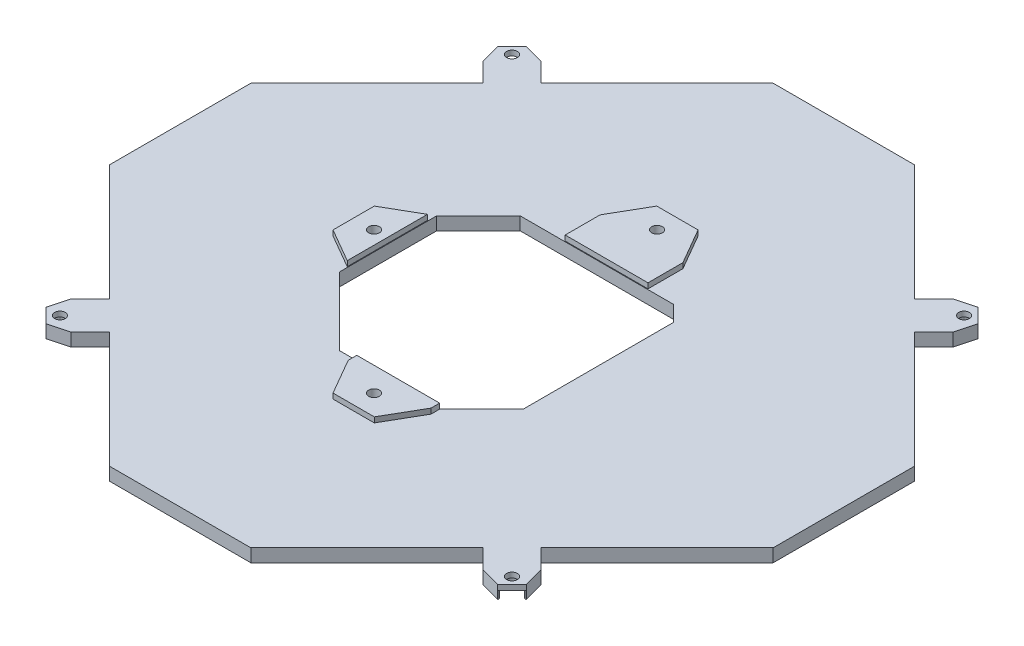
SolidWorks part; units mm, degrees
ref_plane "Front Plane" through (0, 0, 0) normal (0, 0, 1) x (1, 0, 0)
ref_plane "Top Plane" through (0, 0, 0) normal (0, 1, 0) x (1, 0, 0)
ref_plane "Right Plane" through (0, 0, 0) normal (1, 0, 0) x (0, 0, -1)
sketch "Sketch1" plane through (0, -273.8462, 0) normal (0, -1, 0) x (-1, 0, 0)
  line L0 (82.3028, 71.3418) -> (89.3773, 78.4163)
  line L1 (89.3773, 78.4163) -> (91.3931, 85.9396)
  line L2 (91.3931, 85.9396) -> (85.9404, 91.3923)
  line L3 (85.9404, 91.3923) -> (78.4171, 89.3765)
  line L4 (78.4171, 89.3765) -> (71.3427, 82.302)
  line L5 (82.3028, 71.3418) -> (82.02, 71.059)
  line L6 (71.3427, 82.302) -> (71.0598, 82.0192)
  line L7 (71.3418, -82.3028) -> (78.4163, -89.3773)
  line L8 (78.4163, -89.3773) -> (85.9396, -91.3931)
  line L9 (85.9396, -91.3931) -> (91.3923, -85.9404)
  line L10 (91.3923, -85.9404) -> (89.3765, -78.4171)
  line L11 (89.3765, -78.4171) -> (82.302, -71.3427)
  line L12 (71.3418, -82.3028) -> (71.059, -82.02)
  line L13 (82.302, -71.3427) -> (82.0192, -71.0598)
  line L14 (126.6447, 27) -> (126.6447, -27) construction
  line L15 (27, -126.6455) -> (-27, -126.6455) construction
  line L16 (-126.6447, -27) -> (-126.6447, 27) construction
  line L17 (-27, 126.6447) -> (27, 126.6447) construction
  line L18 (126.6447, 27) -> (126.6447, -27) construction
  line L19 (27, -126.6455) -> (-27, -126.6455) construction
  line L20 (-126.6447, -27) -> (-126.6447, 27) construction
  line L21 (-27, 126.6447) -> (27, 126.6447) construction
  line L22 (-126.6447, 27) -> (-27, 126.6447) construction
  line L23 (27, 126.6447) -> (126.6447, 27) construction
  line L24 (126.6447, -27) -> (27, -126.6455) construction
  line L25 (-27, -126.6455) -> (-126.6447, -27) construction
  line L26 (-26.8343, -126.2455) -> (-71.0601, -82.0194)
  line L27 (-126.2447, -26.8343) -> (-126.2447, 26.8343)
  line L28 (-28.1456, -5.25) -> (-32.9992, -5.25)
  line L29 (-32.9992, -5.25) -> (-32.9992, -28.4962)
  line L30 (-32.9992, -28.4962) -> (-17.0954, -44.4)
  line L31 (-17.0954, -44.4) -> (21.2718, -44.4)
  line L32 (21.2718, -44.4) -> (47.1756, -18.4962)
  line L33 (47.1756, -18.4962) -> (47.1756, 18.4962)
  line L34 (47.1756, 18.4962) -> (31.2718, 34.4)
  line L35 (31.2718, 34.4) -> (-27.0954, 34.4)
  line L36 (-27.0954, 34.4) -> (-32.9992, 28.4962)
  line L37 (-32.9992, 28.4962) -> (-32.9992, 5.25)
  line L38 (-32.9992, 5.25) -> (-28.1456, 5.25)
  line L39 (-28.1456, 5.25) -> (-21.4992, 11.8964)
  line L40 (-21.4992, 11.8964) -> (-21.4992, -11.8964)
  line L41 (-21.4992, -11.8964) -> (-28.1456, -5.25)
  line L42 (-28.1456, -5.25) -> (-32.9992, -5.25) construction
  line L43 (-32.9992, -5.25) -> (-32.9992, -28.4962)
  line L44 (-32.9992, -28.4962) -> (-17.0954, -44.4)
  line L45 (-17.0954, -44.4) -> (21.2718, -44.4)
  line L46 (21.2718, -44.4) -> (47.1756, -18.4962)
  line L47 (47.1756, -18.4962) -> (47.1756, 18.4962)
  line L48 (47.1756, 18.4962) -> (31.2718, 34.4)
  line L49 (31.2718, 34.4) -> (-27.0954, 34.4)
  line L50 (-27.0954, 34.4) -> (-32.9992, 28.4962)
  line L51 (-32.9992, 28.4962) -> (-32.9992, 5.25)
  line L52 (-32.9992, 5.25) -> (-28.1456, 5.25) construction
  line L53 (-28.1456, 5.25) -> (-21.4992, 11.8964) construction
  line L54 (-21.4992, 11.8964) -> (-21.4992, -11.8964) construction
  line L55 (-21.4992, -11.8964) -> (-28.1456, -5.25) construction
  line L56 (-126.2447, 26.8343) -> (-82.0192, 71.0598)
  line L57 (-26.8343, 126.2447) -> (26.8343, 126.2447)
  line L58 (26.8343, 126.2447) -> (71.0598, 82.0192)
  line L59 (126.2447, 26.8343) -> (126.2447, -26.8343)
  line L60 (126.2447, -26.8343) -> (82.0193, -71.06)
  line L61 (26.8343, -126.2455) -> (-26.8343, -126.2455)
  line L62 (-82.3028, -71.3418) -> (-89.3773, -78.4163)
  line L63 (-89.3773, -78.4163) -> (-91.3931, -85.9396)
  line L64 (-91.3931, -85.9396) -> (-85.9404, -91.3923)
  line L65 (-85.9404, -91.3923) -> (-78.4171, -89.3765)
  line L66 (-78.4171, -89.3765) -> (-71.3427, -82.302)
  line L67 (-71.3418, 82.3028) -> (-71.059, 82.02)
  line L68 (-82.302, 71.3427) -> (-82.0192, 71.0598)
  line L69 (-82.3028, -71.3418) -> (-82.02, -71.059)
  line L70 (-71.3427, -82.302) -> (-71.0598, -82.0192)
  line L71 (-82.0192, 71.0598) -> (-71.059, 82.02) construction
  line L72 (-71.3418, 82.3028) -> (-78.4163, 89.3773)
  line L73 (-78.4163, 89.3773) -> (-85.9396, 91.3931)
  line L74 (-85.9396, 91.3931) -> (-91.3923, 85.9404)
  line L75 (-89.3765, 78.4171) -> (-82.302, 71.3427)
  line L76 (-91.3923, 85.9404) -> (-89.3765, 78.4171)
  line L77 (-71.3418, 82.3028) -> (-78.4163, 89.3773)
  line L78 (-78.4163, 89.3773) -> (-85.9396, 91.3931)
  line L79 (-85.9396, 91.3931) -> (-91.3923, 85.9404)
  line L80 (-89.3765, 78.4171) -> (-82.302, 71.3427)
  line L81 (-91.3923, 85.9404) -> (-89.3765, 78.4171)
  line L82 (-71.059, 82.02) -> (-26.8343, 126.2447)
  line L83 (-126.2447, 26.8343) -> (-26.8343, 126.2447) construction
  line L84 (71.0598, 82.0192) -> (82.02, 71.059) construction
  line L85 (82.02, 71.059) -> (126.2447, 26.8343)
  line L86 (26.8343, 126.2447) -> (126.2447, 26.8343) construction
  line L87 (82.0193, -71.06) -> (71.0592, -82.0202) construction
  line L88 (71.0592, -82.0202) -> (26.8343, -126.2455)
  line L89 (126.2447, -26.8343) -> (26.8343, -126.2455) construction
  line L90 (-71.0601, -82.0194) -> (-82.0202, -71.0592) construction
  line L91 (-82.0202, -71.0592) -> (-126.2447, -26.8343)
  line L92 (-26.8343, -126.2455) -> (-126.2447, -26.8343) construction
  line L93 (-32.9992, 5.25) -> (-32.9992, -5.25)
  point P65 (0, 0)
  dimension "D1" = 0.25
  dimension "D2" = 0.4
  dimension "D3" = 0.25
  dimension "D4" = 4
extrude "Boss-Extrude1" add sketch "Sketch1" against normal offset from surface (4.95 mm away) 0.05 contours L91 L69 L62 L63 L64 L65 L66 L70 L26 L61 L88 L12 L7 L8 L9 L10 L11 L13 L60 L59 L85 L5 L0 L1 L2 L3 L4 L6 L58 L57 L82 L67 L77 L78 L79 L81 L80 L68 L56 L27 L93 L51 region at (-79.6365, -273.8462, -73.7253)
sketch "Sketch2" plane through (0, -268.8962, 0) normal (0, 1, 0) x (1, 0, 0)
  circle A0 centre (-86.0151, 86.0143) radius 2.05
  circle A1 centre (86.0143, 86.0151) radius 2.05
  circle A2 centre (86.0151, -86.0151) radius 2.05
  circle A3 centre (-86.015, -86.015) radius 2.05
  circle A5 centre (1.3492, 53.8564) radius 2.05
  circle A6 centre (-52.5072, 0) radius 2.05
  circle A7 centre (1.3492, -53.8564) radius 2.05
  dimension "D1" = 4.1
extrude "Cut-Extrude1" cut sketch "Sketch2" against normal through all
sketch "Sketch4" plane through (0, -268.8962, 0) normal (0, 1, 0) x (1, 0, 0)
  line L0 (17.3492, 48) -> (17.3492, 34.4) construction
  line L1 (27.0954, 34.4) -> (-31.2718, 34.4) construction
  line L2 (17.3492, 48) -> (17.3492, 34.15) construction
  line L3 (-14.6508, 48) -> (-14.6508, 34.4) construction
  line L4 (-14.6508, 34.15) -> (-14.6508, 48) construction
  line L5 (-14.6508, 34.4) -> (17.3492, 34.4) construction
  line L6 (17.3492, 48) -> (9.3492, 61.8564) construction
  line L7 (9.3492, 61.8564) -> (-6.6508, 61.8564) construction
  line L8 (-6.6508, 61.8564) -> (-14.6508, 48) construction
  line L9 (-60.5072, 8) -> (-60.5072, -8) construction
  line L10 (-60.5072, -8) -> (-47.1756, -15.697) construction
  line L11 (-47.1756, 18.4962) -> (-47.1756, -18.4962) construction
  line L12 (-46.9256, -15.8413) -> (-60.5072, -8) construction
  line L13 (-60.5072, 8) -> (-47.1756, 15.697) construction
  line L14 (-60.5072, 8) -> (-46.9256, 15.8413) construction
  line L15 (-47.1756, 15.697) -> (-47.1756, -15.697) construction
  line L16 (-14.6508, -44.4) -> (17.3492, -44.4) construction
  line L17 (-21.2718, -44.4) -> (17.0954, -44.4) construction
  line L18 (17.3492, -44.4) -> (17.3492, -48) construction
  line L19 (17.3492, -48) -> (9.3492, -61.8564) construction
  line L20 (-14.6508, -48) -> (-14.6508, -44.4) construction
  line L21 (9.3492, -61.8564) -> (-6.6508, -61.8564) construction
  line L22 (-6.6508, -61.8564) -> (-14.6508, -48) construction
  line L23 (17.0992, 47.933) -> (17.0992, 34.65)
  line L24 (-14.4008, 34.65) -> (17.0992, 34.65)
  line L25 (-14.4008, 47.933) -> (-14.4008, 34.65)
  line L26 (-6.5065, 61.6064) -> (-14.4008, 47.933)
  line L27 (9.2048, 61.6064) -> (-6.5065, 61.6064)
  line L28 (17.0992, 47.933) -> (9.2048, 61.6064)
  line L29 (-60.2572, 7.8557) -> (-60.2572, -7.8557)
  line L30 (-60.2572, -7.8557) -> (-47.4256, -15.264)
  line L31 (-47.4256, 15.264) -> (-47.4256, -15.264)
  line L32 (-60.2572, 7.8557) -> (-47.4256, 15.264)
  line L33 (-14.4008, -44.65) -> (17.0992, -44.65)
  line L34 (17.0992, -44.65) -> (17.0992, -47.933)
  line L35 (17.0992, -47.933) -> (9.2048, -61.6064)
  line L36 (9.2048, -61.6064) -> (-6.5065, -61.6064)
  line L37 (-6.5065, -61.6064) -> (-14.4008, -47.933)
  line L38 (-14.4008, -47.933) -> (-14.4008, -44.65)
  circle A0 centre (1.3492, 53.8564) radius 2.05 construction
  circle A1 centre (-52.5072, 0) radius 2.05 construction
  circle A2 centre (1.3492, -53.8564) radius 2.05 construction
  circle A3 centre (1.3492, 53.8564) radius 2.05
  circle A4 centre (-52.5072, 0) radius 2.05
  circle A5 centre (1.3492, -53.8564) radius 2.05
  dimension "D1" = 0.25
  dimension "D2" = 0.25
  dimension "D3" = 0.25
extrude "Boss-Extrude2" add sketch "Sketch4" along normal blind 2
sketch "Sketch5" plane through (0, -273.8462, 0) normal (0, -1, 0) x (1, 0, 0)
  line L0 (83.6286, 88.4016) -> (86.2799, 91.0529)
  line L1 (91.3931, 85.9396) -> (85.9404, 91.3923) construction
  line L2 (86.2799, 91.0529) -> (91.0529, 86.2799)
  line L3 (91.0529, 86.2799) -> (88.4016, 83.6286)
  line L4 (89.3773, 78.4163) -> (82.0202, 71.0592) construction
  line L5 (88.4016, -83.6286) -> (91.0529, -86.2799)
  line L6 (91.0529, -86.2799) -> (86.2799, -91.0529)
  line L7 (86.2799, -91.0529) -> (83.6286, -88.4016)
  line L8 (-83.6286, -88.4016) -> (-86.2799, -91.0529)
  line L9 (-86.2799, -91.0529) -> (-91.0529, -86.2799)
  line L10 (-91.0529, -86.2799) -> (-88.4016, -83.6286)
  line L11 (-88.4016, 83.6286) -> (-91.0529, 86.2799)
  line L12 (-91.0529, 86.2799) -> (-86.2799, 91.0529)
  line L13 (-86.2799, 91.0529) -> (-83.6286, 88.4016)
  arc A0 (83.6286, 88.4016) -> (88.4016, 83.6286) centre (86.0151, 86.0151) ccw
  circle A1 centre (1.3492, 53.8564) radius 3.375
  circle A2 centre (-52.5072, 0) radius 3.375
  circle A3 centre (1.3492, -53.8564) radius 3.375
  arc A6 (88.4016, 83.6286) -> (83.6286, 88.4016) centre (86.0151, 86.0151) ccw construction
  arc A7 (88.4016, -83.6286) -> (83.6286, -88.4016) centre (86.0151, -86.0151) ccw
  arc A8 (83.6286, -88.4016) -> (88.4016, -83.6286) centre (86.0151, -86.0151) ccw construction
  arc A9 (-83.6286, -88.4016) -> (-88.4016, -83.6286) centre (-86.0151, -86.0151) ccw
  arc A10 (-88.4016, -83.6286) -> (-83.6286, -88.4016) centre (-86.0151, -86.0151) ccw construction
  arc A11 (-88.4016, 83.6286) -> (-83.6286, 88.4016) centre (-86.0151, 86.0151) ccw
  arc A12 (-83.6286, 88.4016) -> (-88.4016, 83.6286) centre (-86.0151, 86.0151) ccw construction
  point P40 (0, 0)
  dimension "D1" = 6.75
  dimension "D2" = 4
extrude "Cut-Extrude2" cut sketch "Sketch5" against normal blind 3
fillet "Fillet1" radius 1 8 edges at (86.2799, -272.3462, -91.0529) (91.0529, -272.3462, -86.2799) (-86.2799, -272.3462, -91.0529) (-91.0529, -272.3462, -86.2799) (-91.0529, -272.3462, 86.2799) (-86.2799, -272.3462, 91.0529) (91.0529, -272.3462, 86.2799) (86.2799, -272.3462, 91.0529)
